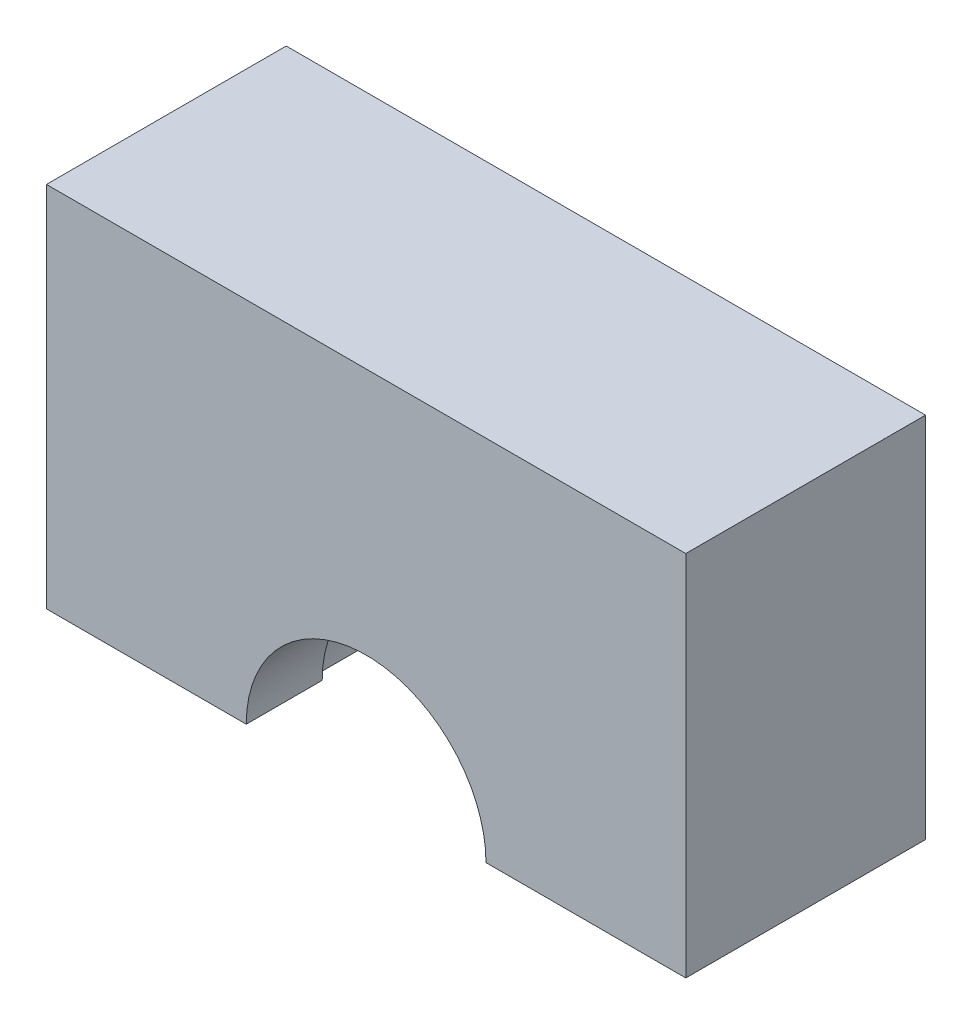
SolidWorks part; units mm, degrees
ref_plane "Front Plane" through (0, 0, 0) normal (0, 0, 1) x (1, 0, 0)
ref_plane "Top Plane" through (0, 0, 0) normal (0, 1, 0) x (1, 0, 0)
ref_plane "Right Plane" through (0, 0, 0) normal (1, 0, 0) x (0, 0, -1)
sketch "Sketch1" plane through (0, 0, 0) normal (0, 0, 1) x (1, 0, 0)
  line L0 (-20, 0) -> (-20, 23)
  line L1 (-20, 23) -> (20, 23)
  line L2 (20, 23) -> (20, 0)
  line L3 (-20, 0) -> (-7.5, 0)
  line L4 (20, 0) -> (7.5, 0)
  arc A0 (7.5, 0) -> (-7.5, 0) centre (0, 0) ccw
  dimension "D1" = 15
  dimension "D2" = 40
  dimension "D3" = 23
extrude "Boss-Extrude1" add sketch "Sketch1" along normal blind 15 contours L2 L1 L0 | L4 L3 A0 region at (0, 12.3836, 0)
sketch "Sketch2" plane through (0, 0, 0) normal (1, 0, 0) x (0, 0, -1)
  line L0 (0, 0) -> (-27.3188, 0) construction
  line L2 (-4.75, 6.4825) -> (-10.25, 6.4825)
  line L3 (-4.75, 6.4825) -> (-4.75, 8)
  line L4 (-4.75, 8) -> (-10.25, 8)
  line L5 (-10.25, 6.4825) -> (-10.25, 8)
  line L6 (-15, 23) -> (0, 23) construction
  point P11 (-7.5, 23)
  point P12 (-7.5, 8)
  dimension "D1" = 8
  dimension "D2" = 5.5
revolve "Cut-Revolve2" cut sketch "Sketch2" angle 360 about L0
